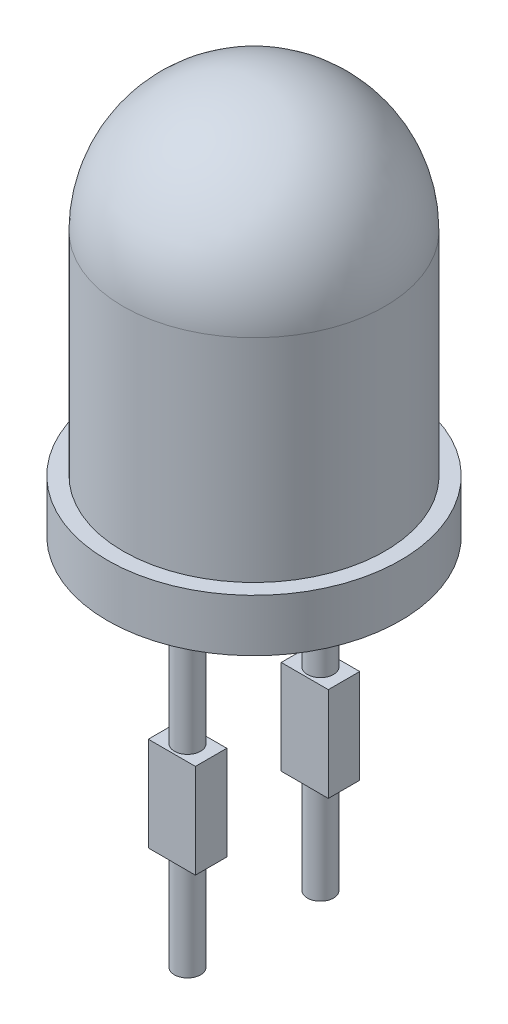
SolidWorks part; units mm, degrees
ref_plane "Front Plane" through (0, 0, 0) normal (0, 0, 1) x (1, 0, 0)
ref_plane "Top Plane" through (0, 0, 0) normal (0, 1, 0) x (1, 0, 0)
ref_plane "Right Plane" through (0, 0, 0) normal (1, 0, 0) x (0, 0, -1)
sketch "Sketch1" plane through (0, 0, 0) normal (1, 0, 0) x (0, 0, -1)
  line L0 (0, 4.525) -> (0, -10.9525) construction
  line L1 (-2.5, 2.025) -> (-2.5, -2.025)
  line L2 (-2.5, -2.025) -> (-2.8, -2.025)
  line L3 (-2.8, -2.025) -> (-2.8, -3.025)
  line L4 (-2.8, -3.025) -> (0, -3.025)
  line L5 (0, 4.525) -> (-4.2269, 4.525) construction
  line L6 (0, 4.525) -> (0, -3.025)
  arc A0 (-2.5, 2.025) -> (0, 4.525) centre (0, 2.025) cw
  point P11 (-2.5, 0)
  dimension "D1" = 5
  dimension "D2" = 7.55
  dimension "D3" = 1
  dimension "D4" = 5.6
revolve "Revolve1" add sketch "Sketch1" angle 360 about L0
sketch "Sketch2" plane through (0, -3.025, 0) normal (0, -1, 0) x (1, 0, 0)
  line L0 (0, 0) -> (3.908, 0) construction
  circle A0 centre (0, 1.27) radius 0.25
  circle A1 centre (0, -1.27) radius 0.25
  dimension "D1" = 2.54
  dimension "D2" = 0.5
extrude "Boss-Extrude1" add sketch "Sketch2" along normal blind 11 separate body
sketch "Sketch3" plane through (0, 0, 0) normal (1, 0, 0) x (0, 0, -1)
  line L0 (1.27, -3.025) -> (1.27, -15.6133) construction
  line L1 (0.97, -5.825) -> (1.57, -5.825)
  line L2 (0.97, -5.825) -> (0.97, -7.625)
  line L3 (0.97, -7.625) -> (1.57, -7.625)
  line L4 (1.57, -5.825) -> (1.57, -7.625)
  line L5 (0.97, -5.825) -> (1.57, -7.625) construction
  line L6 (0.97, -7.625) -> (1.57, -5.825) construction
  line L7 (1.52, -3.025) -> (1.02, -3.025) construction
  line L8 (-2.8, -3.025) -> (2.8, -3.025) construction
  line L9 (0, 0) -> (0, -3.6509) construction
  line L10 (-0.97, -7.625) -> (-1.57, -7.625)
  line L11 (-1.57, -5.825) -> (-1.57, -7.625)
  line L12 (-0.97, -5.825) -> (-1.57, -5.825)
  line L13 (-0.97, -5.825) -> (-0.97, -7.625)
  point P0 (1.27, -6.725)
  dimension "D1" = 0.6
  dimension "D2" = 2.8
  dimension "D3" = 1.8
extrude "Boss-Extrude2" add sketch "Sketch3" along normal mid plane 0.9
sketch "Sketch4" plane through (0, 0, 0) normal (1, 0, 0) x (0, 0, -1)
  line L0 (-2.8, -3.025) -> (2.8, -3.025) construction
  line L1 (-3.8823, -9.525) -> (4.1544, -9.525)
  line L2 (-3.8823, -9.525) -> (-3.8823, -15.3223)
  line L3 (-3.8823, -15.3223) -> (4.1544, -15.3223)
  line L4 (4.1544, -9.525) -> (4.1544, -15.3223)
  dimension "D1" = 6.5
extrude "Cut-Extrude1" cut sketch "Sketch4" against normal through all both and the other way through all
